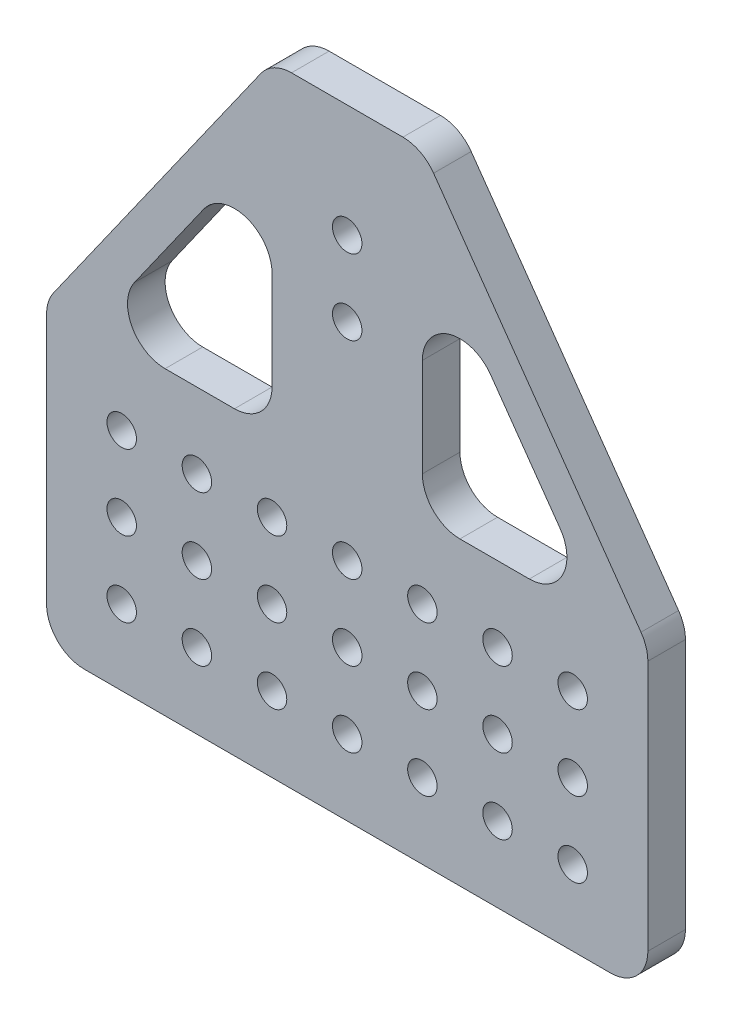
SolidWorks part; units mm, degrees
material "6061-T6 (SS)"
ref_plane "Front Plane" through (0, 0, 0) normal (0, 0, 1) x (1, 0, 0)
ref_plane "Top Plane" through (0, 0, 0) normal (0, 1, 0) x (1, 0, 0)
ref_plane "Right Plane" through (0, 0, 0) normal (1, 0, 0) x (0, 0, -1)
sketch "Sketch1" plane through (0, 0, 0) normal (0, 0, 1) x (1, 0, 0)
  line L1 (0, 104.775) -> (25.4, 104.775)
  line L2 (25.4, 104.775) -> (63.5, 50.8)
  line L3 (63.5, 50.8) -> (63.5, 0)
  line L4 (63.5, 0) -> (0, 0)
  line L5 (0, 104.775) -> (-38.1, 50.8)
  line L6 (-38.1, 50.8) -> (-38.1, 0)
  line L7 (-38.1, 0) -> (0, 0)
  circle A0 centre (12.7, 85.725) radius 2.4892
  circle A1 centre (12.7, 73.025) radius 2.4892
  circle A2 centre (12.7, 12.7) radius 2.4892
  dimension "D8" = 12.7
  dimension "D9" = 4.9784
  dimension "D1" = 104.775
  dimension "D2" = 25.4
  dimension "D3" = 63.5
  dimension "D4" = 50.8
  dimension "D5" = 12.7
  dimension "D7" = 19.05
extrude "Boss-Extrude1" add sketch "Sketch1" along normal mid plane 6.35
pattern_linear "LPattern1" count 4 spacing 12.7 along (1, 0, 0) count 3 spacing 12.7 along (0, 1, 0) of face at (15.1892, 12.7, 3.175)
sketch "Sketch2" plane through (0, 0, 3.175) normal (0, 0, 1) x (1, 0, 0)
  line L0 (25.4, 50.8) -> (25.4, 93.7638)
  line L2 (12.7, 12.7) -> (0, 12.7) construction
  line L3 (55.7274, 50.8) -> (25.4, 93.7638)
  line L4 (25.4, 50.8) -> (55.7274, 50.8)
  line L5 (-38.1, 0) -> (63.5, 0) construction
  line L6 (63.5, 50.8) -> (25.4, 104.775) construction
  line L7 (12.7, 0) -> (12.7, 104.775) construction
  line L8 (-38.1, 0) -> (63.5, 0) construction
  line L9 (25.4, 104.775) -> (0, 104.775) construction
  line L10 (0, 50.8) -> (-30.3274, 50.8)
  line L11 (-30.3274, 50.8) -> (0, 93.7638)
  line L12 (0, 50.8) -> (0, 93.7638)
  circle A0 centre (12.7, 38.1) radius 2.4892 construction
  circle A1 centre (12.7, 25.4) radius 2.4892 construction
  circle A2 centre (12.7, 12.7) radius 2.4892 construction
  circle A3 centre (12.7, 38.1) radius 2.4892
  circle A4 centre (12.7, 25.4) radius 2.4892
  circle A5 centre (12.7, 12.7) radius 2.4892
  circle A6 centre (0, 12.7) radius 2.4892
  circle A7 centre (0, 25.4) radius 2.4892
  circle A8 centre (0, 38.1) radius 2.4892
  circle A9 centre (-12.7, 12.7) radius 2.4892
  circle A10 centre (-12.7, 25.4) radius 2.4892
  circle A11 centre (-12.7, 38.1) radius 2.4892
  circle A12 centre (-25.4, 12.7) radius 2.4892
  circle A13 centre (-25.4, 25.4) radius 2.4892
  circle A14 centre (-25.4, 38.1) radius 2.4892
  point P0 (0, 104.775)
  point P2 (25.4, 104.775)
  dimension "D1" = 4
  dimension "D2" = 50.8
  dimension "D3" = 6.35
  dimension "D4" = 12.7
  dimension "D5" = 12.7
extrude "Cut-Extrude1" cut sketch "Sketch2" against normal through all
fillet "Fillet1" radius 6.35 12 edges at (-38.1, 0, 0) (-38.1, 50.8, 0) (0, 104.775, 0) (25.4, 104.775, 0) (63.5, 0, 0) (-30.3274, 50.8, 0) (0, 50.8, 0) (0, 93.7638, 0) (25.4, 93.7638, 0) (25.4, 50.8, 0) (55.7274, 50.8, 0) (63.5, 50.8, 0)
